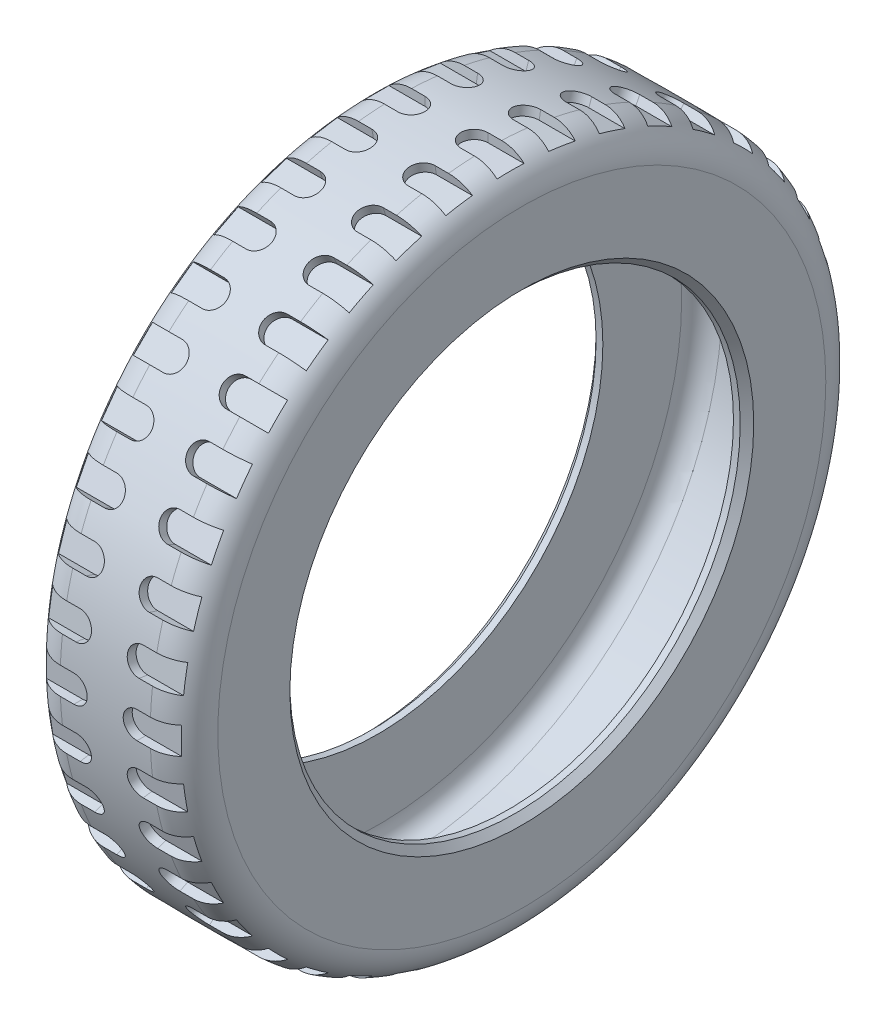
SolidWorks part; units mm, degrees
ref_plane "Ön Düzlem" through (0, 0, 0) normal (0, 0, 1) x (1, 0, 0)
ref_plane "Üst Düzlem" through (0, 0, 0) normal (0, 1, 0) x (1, 0, 0)
ref_plane "Sağ Düzlem" through (0, 0, 0) normal (1, 0, 0) x (0, 0, -1)
sketch "Çizim1" plane through (0, 0, 0) normal (0, 0, 1) x (1, 0, 0)
  line L0 (0, 75) -> (0, 0) construction
  line L1 (0, 0) -> (-110.2508, 0) construction
  line L2 (-17.5, 50) -> (-17.5, 67.5)
  line L3 (-10, 75) -> (10, 75)
  line L4 (17.5, 67.5) -> (17.5, 50)
  line L5 (-14.5, 50) -> (-14.5, 67.5)
  line L6 (-10, 72) -> (10, 72)
  line L7 (14.5, 67.5) -> (14.5, 50)
  line L8 (-17.5, 50) -> (-14.5, 50)
  line L9 (14.5, 50) -> (17.5, 50)
  arc A0 (10, 75) -> (17.5, 67.5) centre (10, 67.5) cw
  arc A1 (-17.5, 67.5) -> (-10, 75) centre (-10, 67.5) cw
  arc A2 (-14.5, 67.5) -> (-10, 72) centre (-10, 67.5) cw
  arc A3 (10, 72) -> (14.5, 67.5) centre (10, 67.5) cw
  point P13 (17.5, 75)
  point P16 (-17.5, 75)
  dimension "D4" = 7.5
  dimension "D1" = 50
  dimension "D2" = 75
  dimension "D3" = 35
  dimension "D5" = 3
revolve "Döndür1" add sketch "Çizim1" angle 360 about L1
chamfer "Pah1" distance 1.5 angle 45 2 edges at (-17.5, 0, -50) (17.5, 0, -50)
ref_plane "Düzlem1" through (0, 75, 0) normal (0, 1, 0) x (1, 0, 0)
sketch "Çizim2" plane through (0, 75, 0) normal (0, 1, 0) x (1, 0, 0)
  line L0 (0, 0) -> (17.5, 0) construction
  line L1 (17.5, -67.5) -> (17.5, 67.5) construction
  line L3 (7, 3) -> (15, 3)
  line L5 (7, -3) -> (15, -3)
  line L6 (15, 3) -> (15, -3)
  arc A0 (7, 3) -> (7, -3) centre (7, 0) ccw
  dimension "D3" = 3
  dimension "D1" = 7
  dimension "D2" = 2.5
  dimension "D4" = 6
  dimension "D5" = 3
extrude "Kes-Ekstrüzyon1" cut sketch "Çizim2" against normal blind 2
pattern_circular "Dairesel Kaplama1" count 40 over 360 about axis through (14.5, 0, 0) along (1, 0, 0) of "Kes-Ekstrüzyon1"
mirror "Aynalama1" about plane through (0, 0, 0) normal (1, 0, 0) of "Dairesel Kaplama1"
